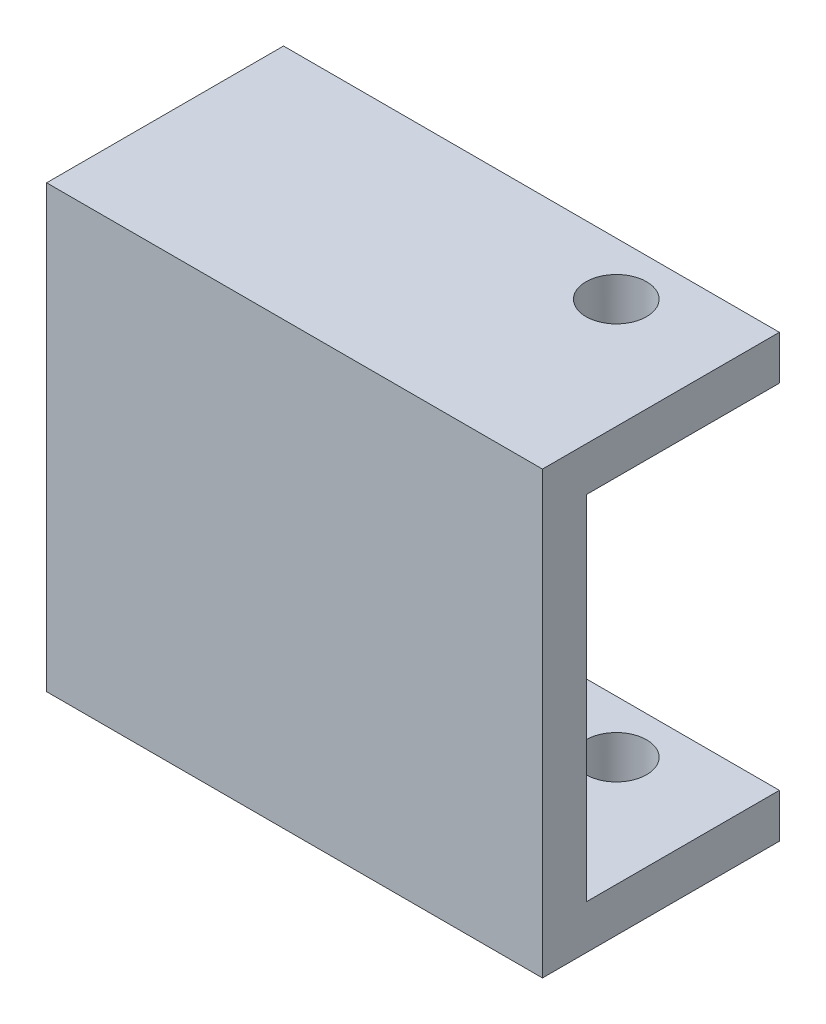
SolidWorks part; units mm, degrees
ref_plane "Front Plane" through (0, 0, 0) normal (0, 0, 1) x (1, 0, 0)
ref_plane "Top Plane" through (0, 0, 0) normal (0, 1, 0) x (1, 0, 0)
ref_plane "Right Plane" through (0, 0, 0) normal (1, 0, 0) x (0, 0, -1)
sketch "Sketch1" plane through (0, 0, 0) normal (0, 0, 1) x (1, 0, 0)
  line L1 (-22.5, 20) -> (22.5, 20)
  line L2 (-22.5, 20) -> (-22.5, -20)
  line L3 (-22.5, -20) -> (22.5, -20)
  line L4 (22.5, 20) -> (22.5, -20)
  line L5 (-22.5, 20) -> (22.5, -20) construction
  line L6 (-22.5, -20) -> (22.5, 20) construction
  point P0 (0, 0)
  dimension "D1" = 40
  dimension "D2" = 45
extrude "Boss-Extrude1" add sketch "Sketch1" along normal blind 4
sketch "Sketch2" plane through (0, 0, 0) normal (0, 0, -1) x (-1, 0, 0)
  line L0 (-22.5, -20) -> (-22.5, 20) construction
  line L1 (22.5, 20) -> (-22.5, 20)
  line L2 (22.5, 20) -> (22.5, 16)
  line L3 (22.5, 16) -> (-22.5, 16)
  line L4 (-22.5, 20) -> (-22.5, 16)
  line L5 (22.5, 0) -> (-22.5, 0) construction
  line L6 (22.5, 20) -> (22.5, -20) construction
  line L7 (22.5, -16) -> (-22.5, -16)
  line L8 (-22.5, -20) -> (-22.5, -16)
  line L9 (22.5, -20) -> (-22.5, -20)
  line L10 (22.5, -20) -> (22.5, -16)
  dimension "D1" = 4
extrude "Boss-Extrude2" add sketch "Sketch2" along normal blind 17.5
sketch "Sketch5" plane through (22.5, 0, 0) normal (1, 0, 0) x (0, 0, -1)
  line L1 (3.81, -6.35) -> (-3.81, -6.35)
  line L2 (3.81, -6.35) -> (3.81, 6.35)
  line L3 (3.81, 6.35) -> (-3.81, 6.35)
  line L4 (-3.81, -6.35) -> (-3.81, 6.35)
  line L5 (3.81, -6.35) -> (-3.81, 6.35) construction
  line L6 (3.81, 6.35) -> (-3.81, -6.35) construction
  line L7 (0, -16) -> (0, 16) construction
  point P6 (0, 0)
  point P7 (0, 0)
  dimension "D1" = 12.7
  dimension "D2" = 7.62
extrude "Cut-Extrude2" [suppressed] cut sketch "Sketch5" against normal blind 7.62
sketch "Sketch6" [suppressed] plane through (0, 0, 3.81) normal (0, 0, -1) x (-1, 0, 0)
  line L1 (-11.43, 6.35) -> (-19.05, 6.35) construction
  line L2 (-19.05, 6.35) -> (-19.05, -6.35) construction
  line L4 (-16.51, 6.35) -> (-19.05, 6.35)
  line L5 (0, 0) -> (-19.05, 0) construction
  line L9 (-19.05, 6.35) -> (-19.05, 4.826)
  line L10 (-19.05, 4.826) -> (-16.51, 4.559)
  line L11 (-16.51, 4.559) -> (-16.51, 6.35)
  line L12 (-19.05, -6.35) -> (-19.05, -4.826)
  line L13 (-19.05, -4.826) -> (-16.51, -4.559)
  line L14 (-16.51, -4.559) -> (-16.51, -6.35)
  line L15 (-16.51, -6.35) -> (-19.05, -6.35)
  dimension "D1" = 2.54
  dimension "D2" = 6
  dimension "D3" = 1.524
extrude "Boss-Extrude3" [suppressed] add sketch "Sketch6" along normal up to surface (3.81 mm away) from surface up to face at (0, 0, 0)
sketch "Sketch7" plane through (0, -20, 0) normal (0, -1, 0) x (1, 0, 0)
  line L0 (22.5, 4) -> (22.5, -17.5) construction
  line L2 (-22.5, 0) -> (22.5, 0) construction
  circle A0 centre (12.5, -12.7) radius 2.75
  circle A1 centre (12.5, -6.35) radius 1.275
  dimension "D1" = 5.5
  dimension "D4" = 2.55
  dimension "D2" = 10
  dimension "D3" = 12.7
  dimension "D5" = 6.35
extrude "Cut-Extrude3" cut sketch "Sketch7" against normal up to surface (40 mm away) contours A0 region at (12.5, -20, -12.7) up to face at (0, 20, -6.75)
extrude "Cut-Extrude4" cut sketch "Sketch7<4>" against normal up to surface (4 mm away) contours A1 region at (12.5, -20, -6.35) up to face at (15.25, -16, -12.7)
sketch "Sketch7<4>" plane through (0, -20, 0) normal (0, -1, 0) x (1, 0, 0) same geometry as "Sketch7"
